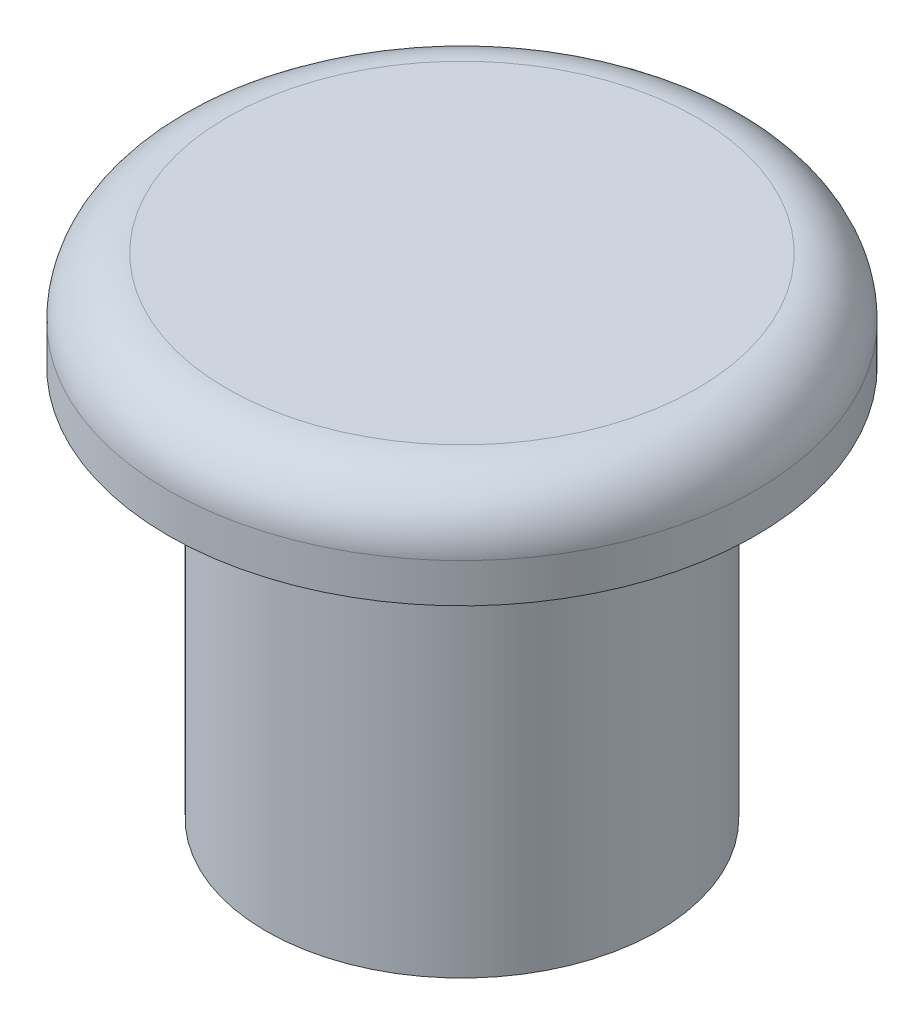
SolidWorks part; units mm, degrees
ref_plane "Front Plane" through (0, 0, 0) normal (0, 0, 1) x (1, 0, 0)
ref_plane "Top Plane" through (0, 0, 0) normal (0, 1, 0) x (1, 0, 0)
ref_plane "Right Plane" through (0, 0, 0) normal (1, 0, 0) x (0, 0, -1)
sketch "Sketch1" plane through (0, 0, 0) normal (0, 1, 0) x (1, 0, 0)
  circle A0 centre (0, 0) radius 1.5
  circle A1 centre (0, 0) radius 1
  dimension "D1" = 2
  dimension "D2" = 3
extrude "Boss-Extrude1" add sketch "Sketch1" along normal blind 0.5 contours A1 | A0 A1 region at (-1.4576, 0, 0) region at (0, 0, 0)
extrude "Boss-Extrude2" add sketch "Sketch1<3>" against normal blind 2 contours A1 region at (0, 0, 0)
sketch "Sketch1<3>" plane through (0, 0, 0) normal (0, 1, 0) x (1, 0, 0) same geometry as "Sketch1"
fillet "Fillet1" radius 0.3 1 edges at (0, 0.5, 1.5)
